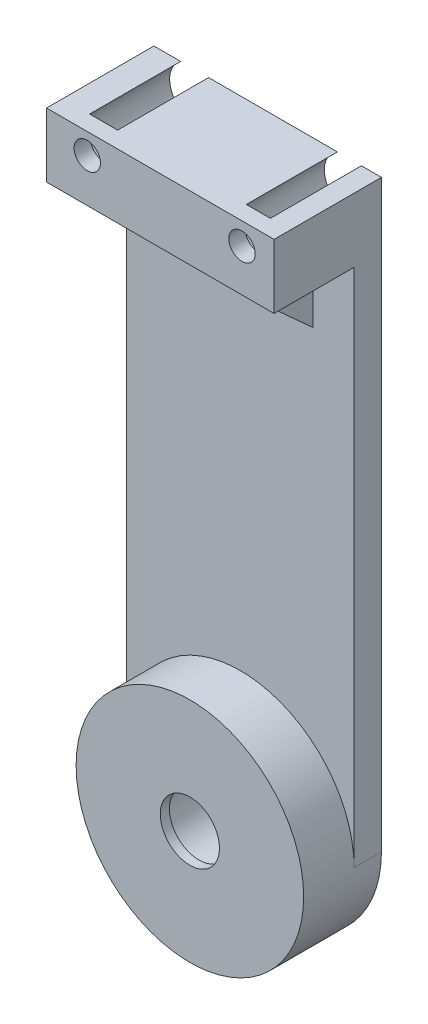
SolidWorks part; units mm, degrees
ref_plane "Plano frontal" through (0, 0, 0) normal (0, 0, 1) x (1, 0, 0)
ref_plane "Plano superior" through (0, 0, 0) normal (0, 1, 0) x (1, 0, 0)
ref_plane "Plano direito" through (0, 0, 0) normal (1, 0, 0) x (0, 0, -1)
other "Centro da massa"
sketch "Esboço2" plane through (0, 0, 0) normal (0, 0, 1) x (1, 0, 0)
  circle A0 centre (-0.4749, -0.0634) radius 12.5
  arc A1 (12.0247, -0.1594) -> (-12.9746, 0.0325) centre (-0.4749, -0.0634) ccw construction
extrude "Ressalto-extrusão1" add sketch "Esboço2" against normal offset from surface (5.55 mm away) 2 offset beyond the face yes
sketch "Esboço4" plane through (0, 0, -5.55) normal (0, 0, -1) x (-1, 0, 0)
  line L0 (-12.0251, -0.0634) -> (-12.0251, 64.1202)
  line L1 (12.9749, -0.0634) -> (12.9749, 64.1202)
  line L2 (12.9749, 64.1202) -> (-12.0251, 64.1202)
  arc A0 (-12.0251, -0.0634) -> (12.9749, -0.0634) centre (0.4749, -0.0634) ccw
  circle A4 centre (0.4749, -0.0634) radius 12.5 construction
  dimension "D1" = 0.5
extrude "Ressalto-extrusão3" add sketch "Esboço4" along normal blind 3
sketch "Esboço5" plane through (0, 0, -8.55) normal (0, 0, -1) x (-1, 0, 0)
  line L0 (12.9749, -0.0634) -> (12.9749, 64.1202) construction
  line L1 (-12.0251, 64.1202) -> (12.9749, 64.1202)
  line L2 (-12.0251, 64.1202) -> (-12.0251, 57.0691)
  line L3 (-12.0251, 57.0691) -> (12.9749, 57.0691)
  line L5 (12.9749, 57.0691) -> (12.9749, 64.1202)
extrude "Ressalto-extrusão4" add sketch "Esboço5" against normal up to surface (11.8 mm away)
hole_wizard "Rebaixo para SHCS M2.51" positions "Esboço6" profile "Esboço7" counterbore size "M2.5" standard "Ansi Metric" end condition up to next
sketch "Esboço6" plane through (0, 0, -8.55) normal (0, 0, -1) x (-1, 0, 0)
  circle A0 centre (-8.4995, 61.7078) radius 1.35 construction
  circle A1 centre (8.5, 61.8383) radius 1.35 construction
  point P0 (-8.4995, 61.7078)
  point P2 (8.5, 61.8383)
sketch "Esboço7" plane through (8.4995, 61.7078, -8.55) normal (1, 0, 0) x (0, 1, 0)
  line L0 (0, 0) -> (0, 11.8)
  line L1 (0, 11.8) -> (1.45, 11.8)
  line L3 (1.45, 11.8) -> (1.45, 10)
  line L4 (1.45, 10) -> (2.75, 10)
  line L5 (2.75, 10) -> (2.75, 0)
  line L7 (2.75, 0) -> (0, 0)
  line L11 (0, -6.35) -> (0, 107.95) construction
  dimension "Thru Hole Dia." = 2.9
  dimension "Thru Hole Depth" = 11.8
  dimension "C'Bore Dia." = 5.5
  dimension "C'Bore Depth" = 10
sketch "Esboço10" plane through (0, 0, 0) normal (1, 0, 0) x (0, 0, -1)
  line L0 (-3.25, 57.0691) -> (5.55, 49.0691)
  line L1 (5.55, -0.0634) -> (5.55, 57.0691) construction
  line L2 (-3.25, 57.0691) -> (5.55, 57.0691) construction
  dimension "D1" = 8
rib "Nervura1" sketch "Esboço10" sketch "Esboço10" thickness 15 extrusion direction parallel to sketch draft on no parameters "D1"=15
sketch "Esboço11" plane through (0, 0, -5.55) normal (0, 0, 1) x (1, 0, 0)
  line L0 (7.5, 49.0691) -> (-7.5, 49.0691) construction
  line L1 (4.5, 49.0691) -> (-4.5, 49.0691)
  line L2 (4.5, 49.0691) -> (4.5, 57.0691)
  line L3 (4.5, 57.0691) -> (-4.5, 57.0691)
  line L4 (-4.5, 49.0691) -> (-4.5, 57.0691)
  line L5 (7.5, 57.0691) -> (-7.5, 57.0691) construction
  line L6 (7.5, 57.0691) -> (7.5, 49.0691) construction
  point P8 (0, 57.0691)
  point P9 (0, 57.0691)
  dimension "D1" = 3
extrude "Corte-extrusão1" cut sketch "Esboço11" along normal up to next
sketch "Esboço12" plane through (0, 0, -8.55) normal (0, 0, -1) x (-1, 0, 0)
  circle A0 centre (0.4749, -0.0634) radius 3.25 construction
  circle A1 centre (0.4749, -0.0634) radius 3.25
extrude "Corte-extrusão2" cut sketch "Esboço12" against normal through all
sketch "Esboço13" plane through (0, 0, -8.55) normal (0, 0, -1) x (-1, 0, 0)
  circle A0 centre (0.4749, -0.0634) radius 4 construction
  circle A1 centre (0.4749, -0.0634) radius 4
extrude "Corte-extrusão3" cut sketch "Esboço13" against normal offset from surface (7.55 mm away) 1 up to face at (2.7751, -0.0634, 0)
